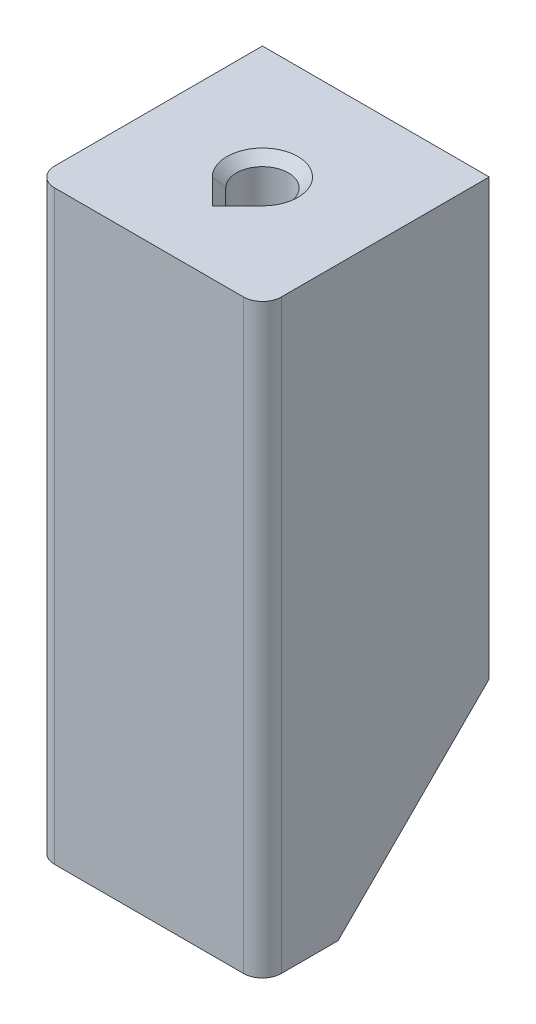
SolidWorks part; units mm, degrees
ref_plane "Front Plane" through (0, 0, 0) normal (0, 0, 1) x (1, 0, 0)
ref_plane "Top Plane" through (0, 0, 0) normal (0, 1, 0) x (1, 0, 0)
ref_plane "Right Plane" through (0, 0, 0) normal (1, 0, 0) x (0, 0, -1)
sketch "Sketch3" plane through (0, 0, 0) normal (1, 0, 0) x (0, 0, -1)
  line L0 (0, 62) -> (-8, 62)
  line L1 (0, 55) -> (0, -55) construction
  line L2 (-8, 62) -> (-8, 0)
  line L3 (55, 0) -> (-55, 0) construction
  line L4 (-8, 0) -> (0, 0)
  line L5 (0, 0) -> (16, 16)
  line L6 (16, 16) -> (16, 62)
  line L7 (16, 62) -> (0, 62)
  dimension "D1" = 45
  dimension "D2" = 62
  dimension "D3" = 8
  dimension "D4" = 16
extrude "Boss-Extrude1" add sketch "Sketch3" along normal blind 12 and the other way blind 12
fillet "Fillet1" radius 2 2 edges at (-12, 31, 8) (12, 31, 8)
sketch "Sketch4" plane through (0, 62, 0) normal (0, 1, 0) x (1, 0, 0)
  line L0 (0, -13.2) -> (0, 13.2) construction
  line L1 (-10, -8) -> (10, -8) construction
  line L2 (-1.9445, 2.0555) -> (0, 0.1109)
  line L3 (0, 0.1109) -> (1.9445, 2.0555)
  circle A0 centre (0, 4) radius 2.75
  dimension "D1" = 5.5
  dimension "D2" = 12
  dimension "D3" = 45
extrude "Cut-Extrude1" cut sketch "Sketch4" against normal through all contours A0 | A0 L2 L3 region at (0, 62, -0.9796) region at (0, 62, -4)
chamfer "Chamfer1" distance 1 3 edges at (0.9723, 62, -1.0832) (-0.9723, 62, -1.0832) (0, 62, -6.75)
